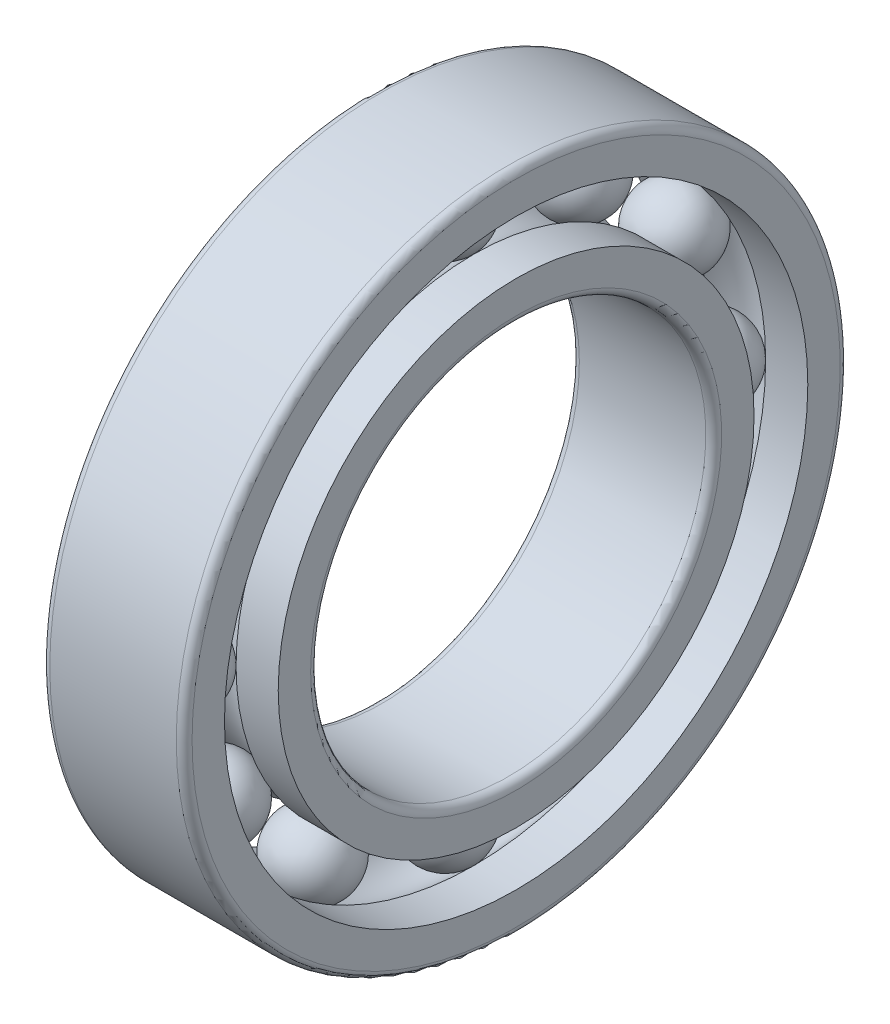
SolidWorks part; units mm, degrees
ref_plane "Спереди" through (0, 0, 0) normal (0, 0, 1) x (1, 0, 0)
ref_plane "Сверху" through (0, 0, 0) normal (0, 1, 0) x (1, 0, 0)
ref_plane "Справа" through (0, 0, 0) normal (1, 0, 0) x (0, 0, -1)
sketch "Эскиз1" plane through (0, 0, 0) normal (0, 0, 1) x (1, 0, 0)
  line L0 (0, 0) -> (13979.1977, 0) construction
  line L1 (0, 15.05) -> (0, 12.5)
  line L2 (0, 12.5) -> (9, 12.5)
  line L3 (9, 12.5) -> (9, 15.05)
  line L6 (9, 18.45) -> (9, 21)
  line L7 (9, 21) -> (0, 21)
  line L8 (0, 21) -> (0, 18.45)
  line L9 (0, 12.5) -> (9, 21) construction
  line L10 (0, 21) -> (9, 12.5) construction
  line L11 (0, 18.45) -> (2.667, 18.45)
  line L12 (6.333, 18.45) -> (9, 18.45)
  line L13 (0, 15.05) -> (2.667, 15.05)
  line L14 (6.333, 15.05) -> (9, 15.05)
  arc A0 (2.667, 18.45) -> (6.333, 18.45) centre (4.5, 16.75) cw
  arc A1 (2.667, 15.05) -> (6.333, 15.05) centre (4.5, 16.75) ccw
  dimension "D5" = 2.5
  dimension "D1" = 42
  dimension "D2" = 9
  dimension "D3" = 25
  dimension "D4" = 2.55
revolve "Повернуть1" add sketch "Эскиз1" angle 360 about L0
fillet "Скругление1" radius 0.5 2 edges at (9, 0, 21) (0, 0, 21)
fillet "Скругление2" radius 0.5 2 edges at (9, 0, 12.5) (0, 0, 12.5)
sketch "Эскиз2" plane through (0, 0, 0) normal (0, 0, 1) x (1, 0, 0)
  line L0 (2.667, 15.05) -> (6.333, 18.45) construction
  line L1 (2.667, 18.45) -> (6.333, 15.05) construction
  line L2 (2, 16.75) -> (7, 16.75) construction
  line L3 (2, 16.75) -> (7, 16.75)
  arc A0 (7, 16.75) -> (2, 16.75) centre (4.5, 16.75) ccw
  dimension "D2" = 2.5
  dimension "D1" = 5
revolve "Повернуть4" add sketch "Эскиз2" angle 360 about L2
pattern_circular "Круговой массив1" count 12 over 360 about axis through (0, 0, 0) along (-1, 0, 0) reverse direction yes of bodies 105
